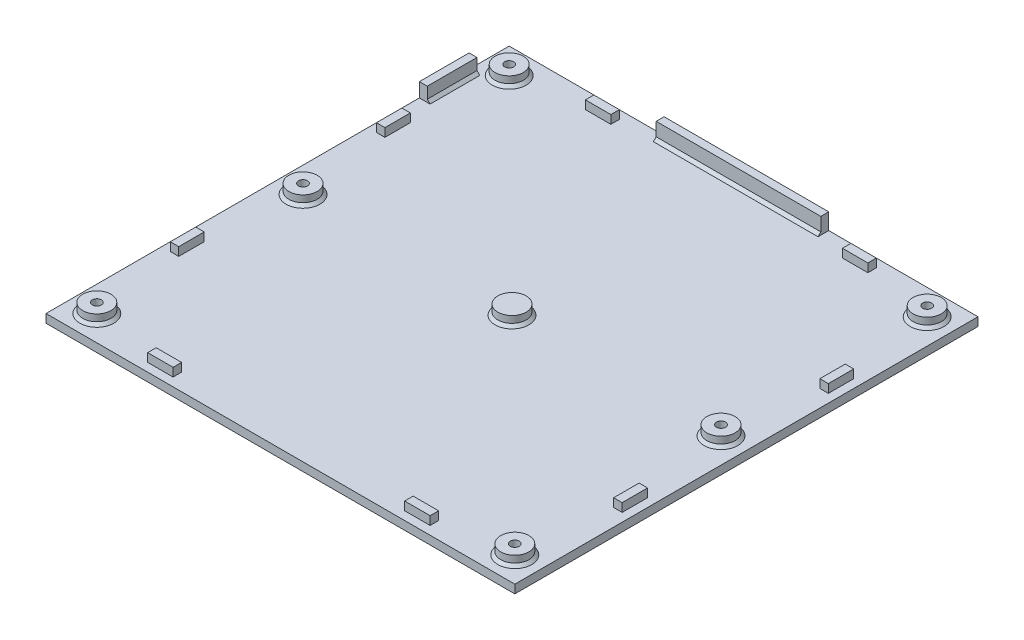
SolidWorks part; units mm, degrees
ref_plane "前视基准面" through (0, 0, 0) normal (0, 0, 1) x (1, 0, 0)
ref_plane "上视基准面" through (0, 0, 0) normal (0, 1, 0) x (1, 0, 0)
ref_plane "右视基准面" through (0, 0, 0) normal (1, 0, 0) x (0, 0, -1)
sketch "草图1" plane through (0, 0, 0) normal (0, 1, 0) x (1, 0, 0)
  line L1 (-83, 82) -> (83, 82)
  line L2 (-83, 82) -> (-83, -82)
  line L3 (-83, -82) -> (83, -82)
  line L4 (83, 82) -> (83, -82)
  line L5 (-83, 82) -> (83, -82) construction
  line L6 (-83, -82) -> (83, 82) construction
  point P0 (0, 0)
  dimension "D1" = 166
  dimension "D2" = 164
extrude "凸台-拉伸1" add sketch "草图1" along normal blind 3
sketch "草图2" plane through (0, 0, 0) normal (0, 1, 0) x (1, 0, 0)
  line L0 (-83, 82) -> (-83, -82) construction
  line L1 (-74, 73) -> (74, 73) construction
  line L2 (-74, 73) -> (-74, -73) construction
  line L3 (-74, -73) -> (74, -73) construction
  line L4 (74, 73) -> (74, -73) construction
  line L5 (83, 82) -> (-83, 82) construction
  line L6 (83, -82) -> (83, 82) construction
  line L7 (-83, -82) -> (83, -82) construction
  circle A0 centre (-74, 73) radius 1.6
  circle A1 centre (-74, 0) radius 1.6
  circle A2 centre (74, 0) radius 1.6
  circle A3 centre (74, 73) radius 1.6
  circle A4 centre (74, -73) radius 1.6
  circle A5 centre (-74, -73) radius 1.6
  dimension "D5" = 3.2
  dimension "D1" = 9
  dimension "D2" = 9
  dimension "D3" = 9
  dimension "D4" = 9
extrude "切除-拉伸1" cut sketch "草图2" along normal up to next
chamfer "倒角1" distance 2 angle 45 6 edges at (74, 0, -71.4) (74, 0, 74.6) (74, 0, 1.6) (-74, 0, -71.4) (-74, 0, 1.6) (-74, 0, 74.6)
sketch "草图3" plane through (0, 0, 0) normal (0, 1, 0) x (1, 0, 0)
  line L0 (83, 82) -> (-83, 82) construction
  line L1 (30.15, 82) -> (-28.15, 82)
  line L2 (30.15, 82) -> (30.15, 79.2)
  line L3 (30.15, 79.2) -> (-28.15, 79.2)
  line L4 (-28.15, 82) -> (-28.15, 79.2)
  line L5 (0, 82) -> (0, 79.2) construction
  point P9 (1, 82)
  point P11 (0, 79.2)
  dimension "D1" = 2.8
  dimension "D2" = 58.3
  dimension "D3" = 1
extrude "凸台-拉伸2" add sketch "草图3" along normal blind 5.75 from surface starting at face at (74, 3, 74.6)
sketch "草图4" plane through (0, 0, 0) normal (0, 1, 0) x (1, 0, 0)
  line L0 (-83, 82) -> (-83, -82) construction
  line L1 (-83, 67.8) -> (-80.2, 67.8)
  line L2 (-83, 67.8) -> (-83, 50.2)
  line L3 (-83, 50.2) -> (-80.2, 50.2)
  line L4 (-80.2, 67.8) -> (-80.2, 50.2)
  line L5 (-28.15, 82) -> (-83, 82) construction
  point P8 (-80.2, 59)
  dimension "D1" = 23
  dimension "D2" = 17.6
  dimension "D3" = 2.8
extrude "凸台-拉伸3" add sketch "草图4" along normal blind 5 from surface starting at face at (74, 3, 74.6)
sketch "草图5" plane through (0, 0, 0) normal (0, 1, 0) x (1, 0, 0)
  circle A0 centre (-74, 73) radius 5
  circle A1 centre (-74, 0) radius 5
  circle A2 centre (-74, -73) radius 5
  circle A3 centre (74, -73) radius 5
  circle A4 centre (74, 0) radius 5
  circle A5 centre (74, 73) radius 5
  circle A6 centre (0, 0) radius 5
  circle A7 centre (74, -73) radius 1.6
  circle A8 centre (74, -73) radius 1.6
  circle A9 centre (-74, -73) radius 1.6
  circle A10 centre (-74, -73) radius 1.6
  circle A11 centre (-74, 0) radius 1.6
  circle A12 centre (-74, 0) radius 1.6
  circle A13 centre (74, 0) radius 1.6
  circle A14 centre (74, 0) radius 1.6
  circle A15 centre (74, 73) radius 1.6
  circle A16 centre (74, 73) radius 1.6
  circle A17 centre (-74, 73) radius 1.6
  circle A18 centre (-74, 73) radius 1.6
  dimension "D1" = 10
  dimension "D2" = 0
  dimension "D3" = 0
  dimension "D4" = 0
  dimension "D5" = 0
  dimension "D6" = 0
  dimension "D7" = 0
extrude "凸台-拉伸4" add sketch "草图5" along normal blind 3.4 from surface starting at face at (-26.8667, 3, -46.5333)
chamfer "倒角2" distance 1 angle 45 9 edges at (74, 3, 78) (-74, 3, 78) (-74, 3, 5) (74, 3, 5) (74, 3, -68) (-80.2, 3, -59) (1, 3, -79.2) (-74, 3, -68) (0, 3, 5)
sketch "草图6" plane through (0, 0, 0) normal (0, 1, 0) x (1, 0, 0)
  line L0 (-80, 79) -> (-83, 79) construction
  line L1 (-80, 79) -> (80, 79) construction
  line L2 (-80, 79) -> (-80, -79) construction
  line L3 (-80, -79) -> (80, -79) construction
  line L4 (80, 79) -> (80, -79) construction
  line L6 (-80, 79) -> (-80, 82) construction
  line L7 (-28.15, 82) -> (-83, 82) construction
  line L8 (80, -79) -> (83, -79) construction
  line L9 (83, -82) -> (83, 82) construction
  line L10 (80, -79) -> (80, -82) construction
  line L11 (-83, -82) -> (83, -82) construction
  line L12 (-83, 50.2) -> (-83, -82) construction
  line L13 (-74, 73) -> (-74, 0) construction
  line L14 (-41, 79) -> (-50, 79)
  line L15 (-41, 79) -> (-41, 76)
  line L16 (-41, 76) -> (-50, 76)
  line L17 (-50, 79) -> (-50, 76)
  line L18 (50, 79) -> (41, 79)
  line L19 (50, 79) -> (50, 76)
  line L20 (50, 76) -> (41, 76)
  line L21 (41, 79) -> (41, 76)
  line L22 (-80, 41) -> (-77, 41)
  line L23 (-80, 41) -> (-80, 32)
  line L24 (-80, 32) -> (-77, 32)
  line L25 (-77, 41) -> (-77, 32)
  line L26 (80, 41) -> (77, 41)
  line L27 (80, 41) -> (80, 32)
  line L28 (80, 32) -> (77, 32)
  line L29 (77, 41) -> (77, 32)
  line L30 (-80, -32) -> (-77, -32)
  line L31 (-80, -32) -> (-80, -41)
  line L32 (-80, -41) -> (-77, -41)
  line L33 (-77, -32) -> (-77, -41)
  line L34 (80, -32) -> (77, -32)
  line L35 (80, -32) -> (80, -41)
  line L36 (80, -41) -> (77, -41)
  line L37 (77, -32) -> (77, -41)
  line L38 (-50, -76) -> (-41, -76)
  line L39 (-50, -76) -> (-50, -79)
  line L40 (-50, -79) -> (-41, -79)
  line L41 (-41, -76) -> (-41, -79)
  line L42 (-74, 0) -> (-74, -73) construction
  line L44 (41, -79) -> (50, -79)
  line L45 (41, -79) -> (41, -76)
  line L46 (41, -76) -> (50, -76)
  line L47 (50, -79) -> (50, -76)
  point P52 (-74, -36.5)
  point P53 (-77, -36.5)
  point P54 (-74, 36.5)
  point P55 (-77, 36.5)
  dimension "D1" = 3
  dimension "D2" = 30
  dimension "D3" = 30
  dimension "D4" = 9
  dimension "D5" = 3
extrude "凸台-拉伸5" add sketch "草图6" along normal blind 3 from surface starting at face at (0, 3, 6)
